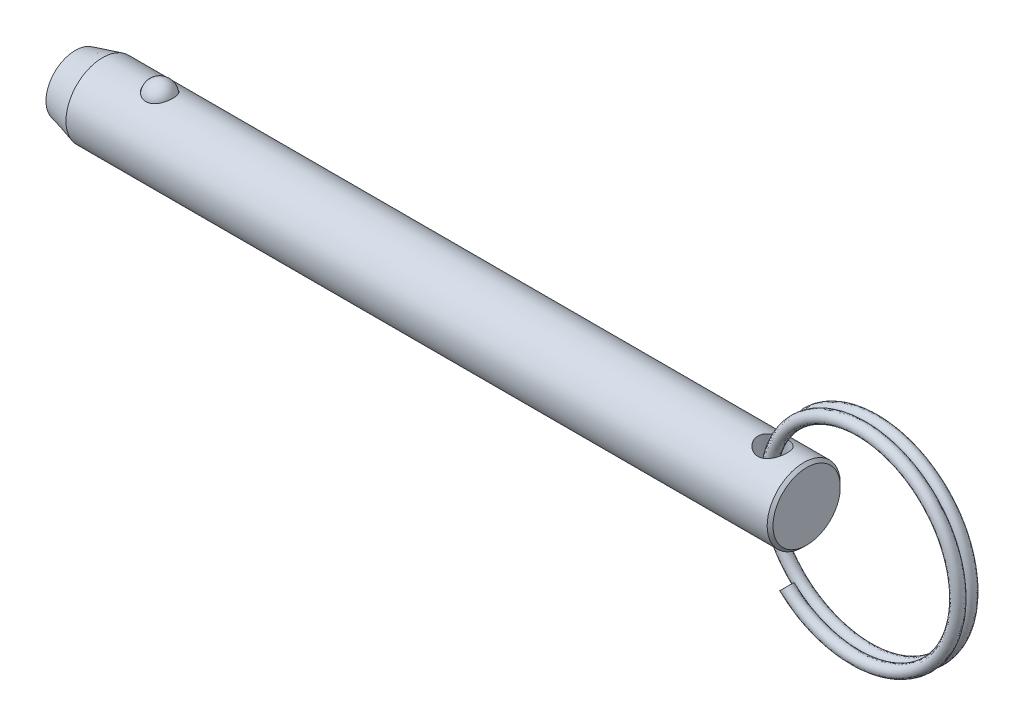
SolidWorks part; units mm, degrees
material "AISI 304"
ref_plane "Front" through (0, 0, 0) normal (0, 0, 1) x (1, 0, 0)
ref_plane "Top" through (0, 0, 0) normal (0, 1, 0) x (1, 0, 0)
ref_plane "Right" through (0, 0, 0) normal (1, 0, 0) x (0, 0, -1)
sketch "Sketch1" plane through (0, 0, 0) normal (0, 0, 1) x (1, 0, 0)
  line L0 (6.35, 4.3815) -> (5.969, 4.7625)
  line L1 (5.969, 4.7625) -> (6.35, 4.7625) construction
  line L4 (6.35, 4.3815) -> (6.35, 0)
  line L5 (6.35, 4.7625) -> (6.35, 4.3815) construction
  line L16 (5.969, 4.7625) -> (-85.3452, 4.7625)
  line L17 (-88.9, 4.7625) -> (-88.9, 3.81) construction
  line L19 (-85.3452, 4.7625) -> (-88.9, 4.7625) construction
  line L22 (-88.9, -4.7625) -> (-85.3452, -4.7625) construction
  line L23 (-77.9064, 4.2863) -> (-77.9064, -4.2863) construction
  line L24 (-88.9, 0) -> (6.35, 0)
  line L27 (6.35, 0) -> (10.7315, 0) construction
  line L29 (-88.9, 0) -> (-88.9, -3.81) construction
  line L36 (0, 0) -> (0, 4.7625) construction
  line L37 (-88.9, 3.81) -> (-88.9, 0)
  line L38 (-85.3452, -4.7625) -> (6.35, -4.7625) construction
  line L39 (-88.9, -3.81) -> (-88.9, -4.7625) construction
  line L40 (-85.3452, 4.7625) -> (-88.9, 3.81)
  line L42 (-85.3452, -4.7625) -> (-88.9, -3.81) construction
  line L43 (-85.3452, 4.7625) -> (-85.3452, -4.7625) construction
  circle A2 centre (-77.9064, 4.2863) radius 1.7717 construction
  point P35 (-76.2, 4.7625)
  dimension "D2" = 8.5725
  dimension "D11" = 1.2954
  dimension "A" = 9.525
  dimension "D" = 6.35
  dimension "E" = 10.8204
  dimension "D3" = 0.381
  dimension "Useable Length" = 76.2
  dimension "D12" = 7.62
  dimension "C" = 12.7
  dimension "A1" = 15
revolve "Revolve1" add sketch "Sketch1" angle 360 about L27
sketch "Sketch2" plane through (0, 0, 0) normal (0, 0, 1) x (1, 0, 0)
  line L0 (-76.1094, 4.2863) -> (-79.7035, 4.2863)
  line L1 (-77.9064, 6.0579) -> (-77.9064, 6.0833) construction
  line L2 (-76.1094, 4.2863) -> (-72.5153, 4.2863) construction
  circle A0 centre (-77.9064, 4.2863) radius 1.7716 construction
  circle A1 centre (-77.9064, 4.2863) radius 1.7717 construction
  arc A2 (-79.7035, 4.2863) -> (-76.1094, 4.2863) centre (-77.9064, 4.2863) cw
  dimension "D1" = 0.0254
revolve "Cut-Revolve1" cut sketch "Sketch2" angle 360 about L2
sketch "Sketch3" plane through (0, 0, 0) normal (0, 0, 1) x (1, 0, 0)
  line L0 (-76.1348, 4.2863) -> (-79.6781, 4.2863)
  line L1 (-76.1348, 4.2863) -> (-72.5915, 4.2863) construction
  circle A0 centre (-77.9064, 4.2863) radius 1.7716 construction
  arc A1 (-76.1348, 4.2863) -> (-79.6781, 4.2863) centre (-77.9064, 4.2863) ccw
revolve "Revolve2" add sketch "Sketch3" angle 360 about L1
sketch "Sketch4" plane through (0, 0, 0) normal (0, 0, 1) x (1, 0, 0)
  line L1 (1.905, -4.7625) -> (3.81, -4.7625)
  line L2 (1.905, -4.7625) -> (1.905, 4.7625)
  line L3 (1.905, 4.7625) -> (3.81, 4.7625)
  line L4 (3.81, -4.7625) -> (3.81, 4.7625)
  line L5 (1.905, -4.7625) -> (1.905, -6.6675) construction
  line L6 (3.81, 4.7625) -> (6.35, 4.7625) construction
  line L8 (0, -4.7625) -> (0, 4.7625) construction
  line L9 (0, 0) -> (1.905, 0) construction
  line L11 (1.905, 0) -> (3.81, 0) construction
  line L12 (5.969, 4.7625) -> (-85.3452, 4.7625) construction
  line L14 (-85.3452, -4.7625) -> (6.35, -4.7625) construction
  dimension "D1" = 3.81
revolve "Cut-Revolve2" cut sketch "Sketch4" angle 360 about L2
sketch "Sketch5" plane through (0, 0, 0) normal (0, 0, 1) x (1, 0, 0)
  line L0 (0, 0) -> (0.6474, 0) construction
  line L1 (0.6474, 0) -> (0.6474, 4.7625) construction
  line L2 (5.969, 4.7625) -> (-85.3452, 4.7625) construction
  line L3 (14.1094, 0) -> (27.5714, 0) construction
  line L4 (3.81, 4.7625) -> (3.1626, 4.7625) construction
  line L5 (1.905, 4.7625) -> (3.81, 4.7625) construction
  line L6 (1.518, 4.7625) -> (1.518, -4.7625) construction
  line L7 (0.6474, 4.7625) -> (0, 4.7625) construction
  line L8 (1.905, -4.7625) -> (3.81, -4.7625) construction
  line L9 (1.518, -4.7625) -> (3.81, -4.7625) construction
  line L10 (0.6474, 0) -> (14.1094, 0) construction
  line L11 (14.1094, 0) -> (9.0642, -10.8195) construction
  line L12 (3.1626, 4.7625) -> (1.518, 4.7625) construction
  line L13 (14.1094, 11.938) -> (14.1094, 13.462) construction
  line L14 (9.0642, -10.8195) -> (8.7422, -11.5101) construction
  circle A0 centre (14.1094, 0) radius 13.462
  circle A1 centre (14.1094, 0) radius 11.938 construction
  circle A2 centre (14.1094, 0) radius 12.7 construction
  point P26 (14.1094, 12.7)
  dimension "D1" = 65
  dimension "R Ring Dia" = 25.4
  dimension "Ring OD" = 1.524
curve "Helix/Spiral1" pitch 1.5494 height 1.3557 radius 13.462 left hand yes centre (14.1094, 0, 0) axis (0, 0, -1) start towards (1, 0, 0)
sketch "Sketch6" plane through (114.0038, 0, 0) normal (0, 1, 0) x (0, 0, -1)
  line L0 (0, 111.8324) -> (0, 112.5944) construction
  line L1 (0, 112.5944) -> (0, 113.3564) construction
  circle A0 centre (0, 112.5944) radius 0.762
  dimension "D1" = 1.524
sketch "Sketch7" plane through (0, 0, 0) normal (0, 0, 1) x (1, 0, 0)
  circle A0 centre (14.1094, 0) radius 13.462 construction
  circle A1 centre (14.1094, 0) radius 13.462
curve "Helix/Spiral2" pitch 1.5494 height 1.3557 radius 13.462 left hand yes centre (14.1094, 0, 0) axis (0, 0, 1) start towards (1, 0, 0)
sweep "Sweep1" add profiles "Sketch6" path "Helix/Spiral1"
sweep "Sweep2" add profiles "Sketch6<2>" path "Helix/Spiral2"
sketch "Sketch6<2>" plane through (114.0038, 0, 0) normal (0, 1, 0) x (0, 0, -1) same geometry as "Sketch6"
ref_plane "Plane1" through (0, -10.8195, 0) normal (0, 1, 0) x (-1, 0, 0)
sketch "Sketch8" plane through (0, -10.8195, 0) normal (0, 1, 0) x (-1, 0, 0)
  line L0 (295.7358, 0) -> (-9.0642, 0) construction
  line L1 (9.9858, -0.7779) -> (4.1522, -0.7779)
  line L2 (3.146, -0.9415) -> (-7.555, -4.517)
  line L3 (-7.555, 4.517) -> (3.146, 0.9415)
  line L4 (4.1522, 0.7779) -> (282.5194, 0.7779)
  line L5 (283.5256, 0.9415) -> (294.2265, 4.517)
  line L6 (276.6858, -0.7779) -> (282.5194, -0.7779)
  line L7 (283.5256, -0.9415) -> (294.2265, -4.517)
  line L8 (9.9858, -0.7779) -> (9.9858, 0.7779) construction
  arc A0 (-7.555, 4.517) -> (-7.555, -4.517) centre (-9.0642, 0) ccw
  arc A1 (294.2265, -4.517) -> (294.2265, 4.517) centre (295.7358, 0) ccw
  arc A2 (4.1522, -0.7779) -> (3.146, -0.9415) centre (4.1522, -3.9529) ccw
  arc A3 (3.146, 0.9415) -> (4.1522, 0.7779) centre (4.1522, 3.9529) ccw
  arc A4 (282.5194, -0.7779) -> (283.5256, -0.9415) centre (282.5194, -3.9529) cw
  arc A5 (282.5194, 0.7779) -> (283.5256, 0.9415) centre (282.5194, 3.9529) ccw
  point P6 (9.9858, 0)
  point P16 (3.6358, -0.7779)
  point P20 (3.6358, 0.7779)
  point P23 (283.0358, -0.7779)
  point P26 (283.0358, 0.7779)
  dimension "D2" = 4.7625
  dimension "D3" = 1.5557
  dimension "D6" = 3.175
  dimension "Lanyard Length" = 304.8
  dimension "D4" = 6.35
  dimension "D5" = 12.7
ref_plane "Plane2" through (-9.9858, 0, 0) normal (1, 0, 0) x (0, 0, -1)
sketch "Sketch9" plane through (-9.9858, 0, 0) normal (1, 0, 0) x (0, 0, -1)
  circle A0 centre (0.7779, -10.8195) radius 0.7779
sweep "Sweep3" [suppressed] add profiles "Sketch9" path "Sketch8"
sketch "Sketch10" [suppressed] plane through (-9.9858, 0, 0) normal (1, 0, 0) x (0, 0, -1)
  arc A0 (-0.3849, -10.1482) -> (-0.3849, -11.4908) centre (-0.7779, -10.8195) ccw
  circle A1 centre (0.7779, -10.8195) radius 0.7779
  arc A2 (0.3849, -11.4908) -> (0.3849, -10.1482) centre (0.7779, -10.8195) ccw
  arc A3 (-0.3849, -11.4908) -> (0.3849, -11.4908) centre (0, -12.1485) cw
  arc A4 (-0.3869, -9.3301) -> (-0.3869, -12.3089) centre (-0.7779, -10.8195) ccw
  arc A5 (0.3869, -12.3089) -> (0.3869, -9.3301) centre (0.7779, -10.8195) ccw
  circle A6 centre (-0.7779, -10.8195) radius 1.5399 construction
  circle A7 centre (-0.7779, -10.8195) radius 0.7779 construction
  arc A8 (-0.3849, -10.1482) -> (0.3849, -10.1482) centre (0, -9.4905) ccw
  arc A9 (-0.3869, -9.3301) -> (0.3869, -9.3301) centre (0, -7.856) ccw
  arc A10 (0.3869, -12.3089) -> (-0.3869, -12.3089) centre (0, -13.783) ccw
  point P4 (-0.034, -10.2746)
  point P8 (2.3178, -10.502)
  point P9 (0.762, -10.502)
  dimension "D3" = 1.524
  dimension "D4" = 0.762
  dimension "D2" = 0.762
  dimension "D1" = 0
extrude "Extrude1" [suppressed] add sketch "Sketch10" along normal blind 5.715 separate body
sketch "Sketch11" [suppressed] plane through (-276.6858, 0, 0) normal (1, 0, 0) x (0, 0, -1)
  arc A4 (-0.3849, -10.1482) -> (-0.3849, -11.4908) centre (-0.7779, -10.8195) ccw
  arc A5 (0.3849, -11.4908) -> (-0.3849, -11.4908) centre (0, -12.1485) ccw
  arc A6 (0.3849, -11.4908) -> (0.3849, -10.1482) centre (0.7779, -10.8195) ccw
  arc A7 (-0.3849, -10.1482) -> (0.3849, -10.1482) centre (0, -9.4905) ccw
  arc A8 (-0.3849, -10.1482) -> (-0.3849, -11.4908) centre (-0.7779, -10.8195) ccw
  arc A9 (0.3849, -11.4908) -> (-0.3849, -11.4908) centre (0, -12.1485) ccw
  arc A10 (0.3849, -11.4908) -> (0.3849, -10.1482) centre (0.7779, -10.8195) ccw
  arc A11 (-0.3849, -10.1482) -> (0.3849, -10.1482) centre (0, -9.4905) ccw
  arc A12 (-0.3869, -9.3301) -> (-0.3869, -12.3089) centre (-0.7779, -10.8195) ccw
  arc A13 (0.3869, -12.3089) -> (-0.3869, -12.3089) centre (0, -13.783) ccw
  arc A14 (0.3869, -12.3089) -> (0.3869, -9.3301) centre (0.7779, -10.8195) ccw
  arc A15 (-0.3869, -9.3301) -> (0.3869, -9.3301) centre (0, -7.856) ccw
  arc A16 (-0.3869, -9.3301) -> (-0.3869, -12.3089) centre (-0.7779, -10.8195) ccw
  arc A17 (0.3869, -12.3089) -> (-0.3869, -12.3089) centre (0, -13.783) ccw
  arc A18 (0.3869, -12.3089) -> (0.3869, -9.3301) centre (0.7779, -10.8195) ccw
  arc A19 (-0.3869, -9.3301) -> (0.3869, -9.3301) centre (0, -7.856) ccw
  dimension "D1" = 0
  dimension "D2" = 0
extrude "Extrude2" [suppressed] add sketch "Sketch11" against normal blind 5.715 separate body
sketch "Sketch12" plane through (0, -10.8195, 0) normal (0, 1, 0) x (-1, 0, 0)
  line L0 (326.5167, -5.2864) -> (320.9541, -5.2864) construction
  line L1 (326.5167, -5.9214) -> (310.1482, -5.9214)
  line L2 (326.5167, -5.9214) -> (326.5167, -4.6514)
  line L3 (326.5167, -4.6514) -> (310.3721, -4.6514)
  line L4 (310.1482, -5.9214) -> (310.3721, -4.6514) construction
  line L5 (310.1482, -5.9214) -> (294.7667, -0.3231)
  line L6 (320.9541, -5.2864) -> (310.2601, -5.2864) construction
  line L7 (310.3721, -4.6514) -> (295.2011, 0.8704)
  line L8 (294.7667, -0.3231) -> (295.2011, 0.8704)
  line L9 (310.2601, -5.2864) -> (300.2111, -1.6289) construction
  line L10 (300.2111, -1.6289) -> (294.9839, 0.2737) construction
  arc A0 (294.2265, -4.517) -> (294.2265, 4.517) centre (295.7358, 0) ccw construction
  dimension "D1" = 20
  dimension "D2" = 31.75
  dimension "D3" = 1.27
  dimension "D4" = 5.5626
extrude "Extrude3" [suppressed] add sketch "Sketch12" along normal mid plane 12.7 separate body
sketch "Sketch13" [suppressed] plane through (0, 0, -4.6514) normal (0, 0, 1) x (1, 0, 0)
  line L0 (-326.5167, -10.8195) -> (-310.3721, -10.8195) construction
  line L1 (-324.5237, -4.4695) -> (-326.5167, -4.4695)
  line L2 (-326.5167, -4.4695) -> (-310.3721, -4.4695) construction
  line L3 (-326.5167, -4.4695) -> (-328.5097, -4.4695)
  line L4 (-328.5097, -4.4695) -> (-328.5097, -17.1695)
  line L5 (-328.5097, -17.1695) -> (-326.5167, -17.1695)
  line L6 (-326.5167, -17.1695) -> (-324.5237, -17.1695)
  line L7 (-326.5167, -17.1695) -> (-310.3721, -17.1695) construction
  arc A0 (-324.5237, -4.4695) -> (-324.5237, -17.1695) centre (-315.4042, -10.8195) ccw
  circle A1 centre (-320.9541, -10.8195) radius 2.5781
  dimension "D1" = 5.1562
  dimension "D2" = 11.1125
extrude "Extrude4" [suppressed] cut sketch "Sketch13" against normal up to surface (1.27 mm away)
sketch "Sketch14" [suppressed] plane through (-34.8117, 0, 95.6443) normal (-0.342, 0, 0.9397) x (0.9397, 0, 0.342)
  line L3 (-279.0936, -4.4695) -> (-277.1006, -4.4695)
  line L4 (-277.1006, -4.4695) -> (-275.1076, -4.4695)
  line L5 (-275.1076, -4.4695) -> (-275.1076, -17.1695)
  line L6 (-275.1076, -17.1695) -> (-277.1006, -17.1695)
  line L7 (-277.1006, -17.1695) -> (-279.0936, -17.1695)
  line L8 (-277.1006, -4.4695) -> (-277.1006, -17.1695) construction
  line L9 (-293.2453, -4.4695) -> (-277.1006, -4.4695) construction
  line L10 (-293.3572, -10.8195) -> (-282.6632, -10.8195) construction
  arc A0 (-279.0936, -17.1695) -> (-279.0936, -4.4695) centre (-288.2131, -10.8195) ccw
  circle A1 centre (-282.6632, -10.8195) radius 2.5781
  dimension "D1" = 5.1562
  dimension "D2" = 11.1125
extrude "Extrude6" [suppressed] cut sketch "Sketch14" against normal up to surface (1.27 mm away)
sketch "Sketch15" [suppressed] plane through (0, 0, 0) normal (0, 0, 1) x (1, 0, 0)
  line L1 (-257.4541, -4.4695) -> (-98.7041, -4.4695)
  line L2 (-257.4541, -4.4695) -> (-270.1541, -17.1695)
  line L3 (-270.1541, -17.1695) -> (-111.4041, -17.1695)
  line L4 (-98.7041, -4.4695) -> (-111.4041, -17.1695)
  line L5 (-324.5237, -4.4695) -> (-310.3721, -4.4695) construction
  line L6 (-324.5237, -17.1695) -> (-310.3721, -17.1695) construction
  circle A0 centre (-320.9541, -10.8195) radius 2.5781 construction
  dimension "D1" = 63.5
  dimension "D2" = 158.75
  dimension "D3" = 45
extrude "Extrude7" [suppressed] cut sketch "Sketch15" against normal through all and the other way through all
move or copy body "Body-Move/Copy1" [suppressed] bodies to move or copy 147 151 144 copy no translate (152.4, 0, 0)
sketch "Sketch16" [suppressed] plane through (0, 0, 0) normal (0, 0, 1) x (1, 0, 0)
  line L0 (-111.4041, -6.057) -> (-111.4041, -9.232) construction
  line L1 (-111.4041, -9.232) -> (-108.8641, -8.2795) construction
  line L2 (-108.8641, -8.2795) -> (-113.9441, -13.3595) construction
  line L3 (-113.9441, -13.3595) -> (-111.4041, -12.407) construction
  line L4 (-111.4041, -12.407) -> (-111.4041, -15.582) construction
  line L5 (-112.182, -11.5974) -> (-110.6263, -10.0416) construction
  line L6 (-105.0541, -15.582) -> (-105.0541, -12.407) construction
  line L7 (-105.0541, -12.407) -> (-107.5941, -13.3595) construction
  line L8 (-107.5941, -13.3595) -> (-102.5141, -8.2795) construction
  line L9 (-102.5141, -8.2795) -> (-105.0541, -9.232) construction
  line L10 (-105.0541, -9.232) -> (-105.0541, -6.057) construction
  line L11 (-104.2763, -10.0416) -> (-105.832, -11.5974) construction
  line L14 (-4.1522, -10.8195) -> (-282.5194, -10.8195) construction
  dimension "D1" = 3.175
  dimension "D2" = 3.175
  dimension "D3" = 5.08
  dimension "D4" = 1.5875
equation "\"D12@Sketch1\"=\"A@Sketch1\" * 0.80"
equation "\"D2@Sketch1\"=\"A@Sketch1\" * 0.9"
equation "\"D1@Sketch4\" = \"A@Sketch1\" / 2.5"
equation "\"Ring OD@Sketch5\" = \"R Ring Dia@Sketch5\" * 0.06"
equation "\"D4@Helix/Spiral1\"=\"Ring OD@Sketch5\" + 0.001"
equation "\"D1@Sketch6\"=\"Ring OD@Sketch5\""
equation "\"D4@Helix/Spiral2\" = \"D4@Helix/Spiral1\""
equation "\"D5@Helix/Spiral2\" = \"D5@Helix/Spiral1\""
equation "\"D1@Sketch14\" = \"D1@Sketch13\""
equation "\"D2@Sketch14\" = \"D2@Sketch13\""
